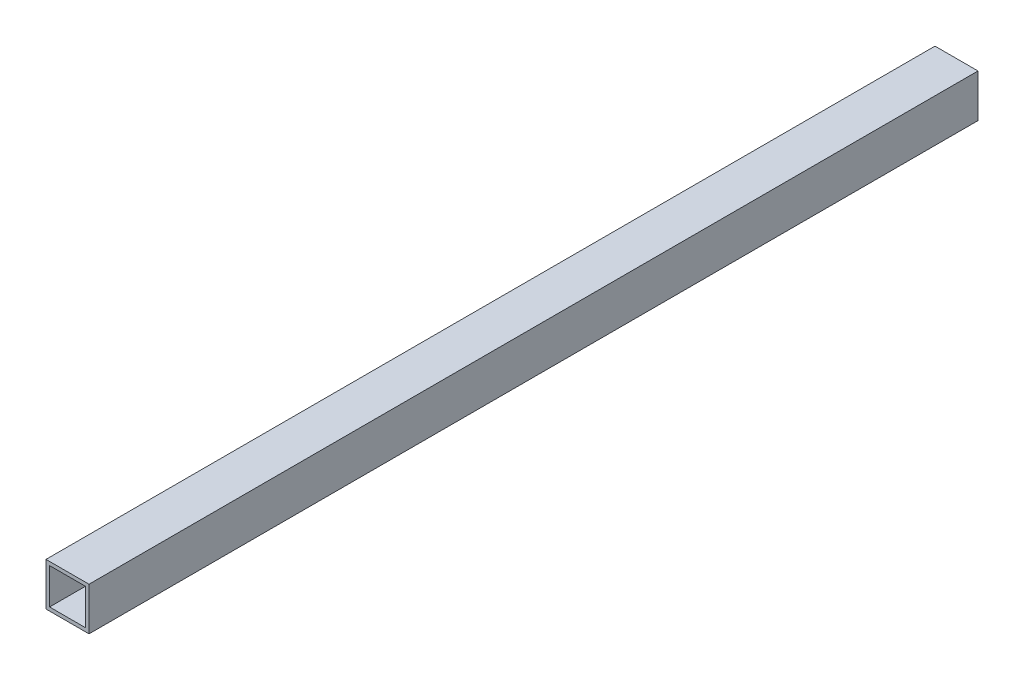
SolidWorks part; units mm, degrees
material "6061 Alloy"
ref_plane "Front Plane" through (0, 0, 0) normal (0, 0, 1) x (1, 0, 0)
ref_plane "Top Plane" through (0, 0, 0) normal (0, 1, 0) x (1, 0, 0)
ref_plane "Right Plane" through (0, 0, 0) normal (1, 0, 0) x (0, 0, -1)
sketch "Sketch1" plane through (0, 0, 0) normal (0, 0, 1) x (1, 0, 0)
  line L1 (-7.9375, -7.9375) -> (7.9375, -7.9375)
  line L2 (-7.9375, -7.9375) -> (-7.9375, 7.9375)
  line L3 (-7.9375, 7.9375) -> (7.9375, 7.9375)
  line L4 (7.9375, -7.9375) -> (7.9375, 7.9375)
  line L5 (-7.9375, -7.9375) -> (7.9375, 7.9375) construction
  line L6 (-7.9375, 7.9375) -> (7.9375, -7.9375) construction
  line L7 (-9.525, -9.525) -> (9.525, -9.525)
  line L8 (-9.525, -9.525) -> (-9.525, 9.525)
  line L9 (-9.525, 9.525) -> (9.525, 9.525)
  line L10 (9.525, -9.525) -> (9.525, 9.525)
  line L11 (-9.525, -9.525) -> (9.525, 9.525) construction
  line L12 (-9.525, 9.525) -> (9.525, -9.525) construction
  point P0 (0, 0)
  point P6 (0, 0)
  dimension "D1" = 19.05
  dimension "D2" = 19.05
  dimension "D3" = 1.5875
  dimension "D4" = 1.5875
extrude "Boss-Extrude1" add sketch "Sketch1" along normal mid plane 393.7
